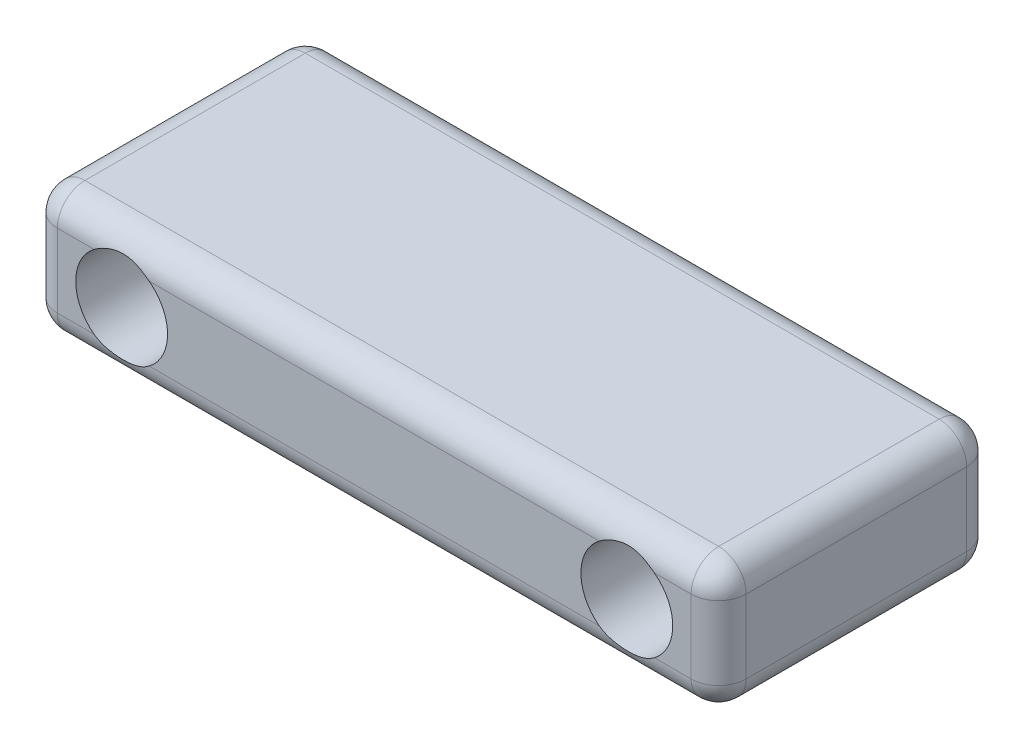
SolidWorks part; units mm, degrees
ref_plane "Front Plane" through (0, 0, 0) normal (0, 0, 1) x (1, 0, 0)
ref_plane "Top Plane" through (0, 0, 0) normal (0, 1, 0) x (1, 0, 0)
ref_plane "Right Plane" through (0, 0, 0) normal (1, 0, 0) x (0, 0, -1)
sketch "Sketch1" plane through (0, 0, 0) normal (0, 0, 1) x (1, 0, 0)
  line L0 (-37.5, 0) -> (37.5, 0) construction
  line L1 (-37.5, -7) -> (37.5, -7)
  line L2 (-37.5, -7) -> (-37.5, 7)
  line L3 (-37.5, 7) -> (37.5, 7)
  line L4 (37.5, -7) -> (37.5, 7)
  line L5 (-37.5, -7) -> (37.5, 7) construction
  line L6 (-37.5, 7) -> (37.5, -7) construction
  line L7 (0, 0) -> (-37.5, 0) construction
  line L8 (-37.5, 0) -> (0, 0) construction
  line L9 (0, 0) -> (37.5, 0) construction
  line L10 (0, 7) -> (0, -7) construction
  circle A0 centre (27.5, 0) radius 5
  circle A1 centre (-27.5, 0) radius 5
  point P0 (0, 0)
  dimension "D3" = 10
  dimension "D6" = 10
  dimension "D1" = 75
  dimension "D2" = 14
  dimension "D4" = 10
  dimension "D5" = 10
extrude "Boss-Extrude1" add sketch "Sketch1" along normal blind 30
fillet "Fillet1" radius 3 12 edges at (0, -7, 30) (0, -7, 0) (37.5, -7, 15) (37.5, 0, 30) (37.5, 0, 0) (37.5, 7, 15) (0, 7, 30) (0, 7, 0) (-37.5, 7, 15) (-37.5, 0, 30) (-37.5, -7, 15) (-37.5, 0, 0)
